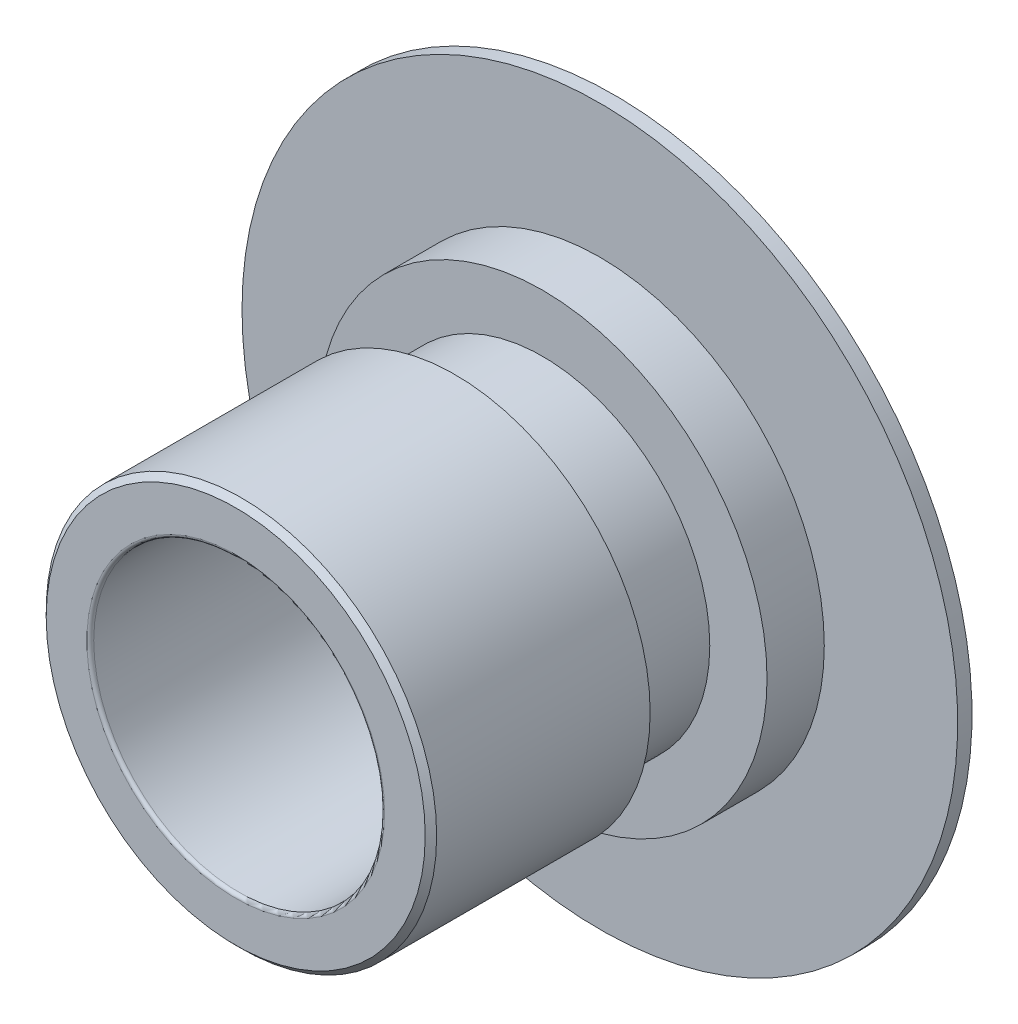
SolidWorks part; units mm, degrees
ref_plane "Front Plane" through (0, 0, 0) normal (0, 0, 1) x (1, 0, 0)
ref_plane "Top Plane" through (0, 0, 0) normal (0, 1, 0) x (1, 0, 0)
ref_plane "Right Plane" through (0, 0, 0) normal (1, 0, 0) x (0, 0, -1)
sketch "Sketch1" plane through (0, 0, 0) normal (0, 0, 1) x (1, 0, 0)
  circle A0 centre (0, 0) radius 3.2258
  circle A1 centre (0, 0) radius 4.3307
extrude "Extrude1" add sketch "Sketch1" along normal blind 6.8072
sketch "Sketch2" plane through (0, 0, 0) normal (0, 0, -1) x (-1, 0, 0)
  circle A0 centre (0, 0) radius 3.2258
  circle A1 centre (0, 0) radius 4.9784
extrude "Extrude2" add sketch "Sketch2" along normal blind 1.27
sketch "Sketch3" plane through (0, 0, -1.27) normal (0, 0, -1) x (-1, 0, 0)
  circle A0 centre (0, 0) radius 3.2258
  circle A1 centre (0, 0) radius 7.9375
extrude "Extrude3" add sketch "Sketch3" along normal blind 0.3175
sketch "Sketch4" plane through (0, 0, 0) normal (0, 0, 1) x (1, 0, 0)
  circle A0 centre (0, 0) radius 4.3434
  circle A1 centre (0, 0) radius 3.7084
extrude "Cut-Extrude1" cut sketch "Sketch4" along normal blind 1.778
chamfer "Chamfer1" distance 0.6223 angle 15 1 edges at (4.3307, 0, 1.778) first distance on face at (3.7084, 0, 1.778)
chamfer "Chamfer2" distance 0.127 angle 45 1 edges at (4.3307, 0, 6.8072)
fillet "Fillet2" radius 0.0762 1 edges at (3.2258, 0, 6.8072)
